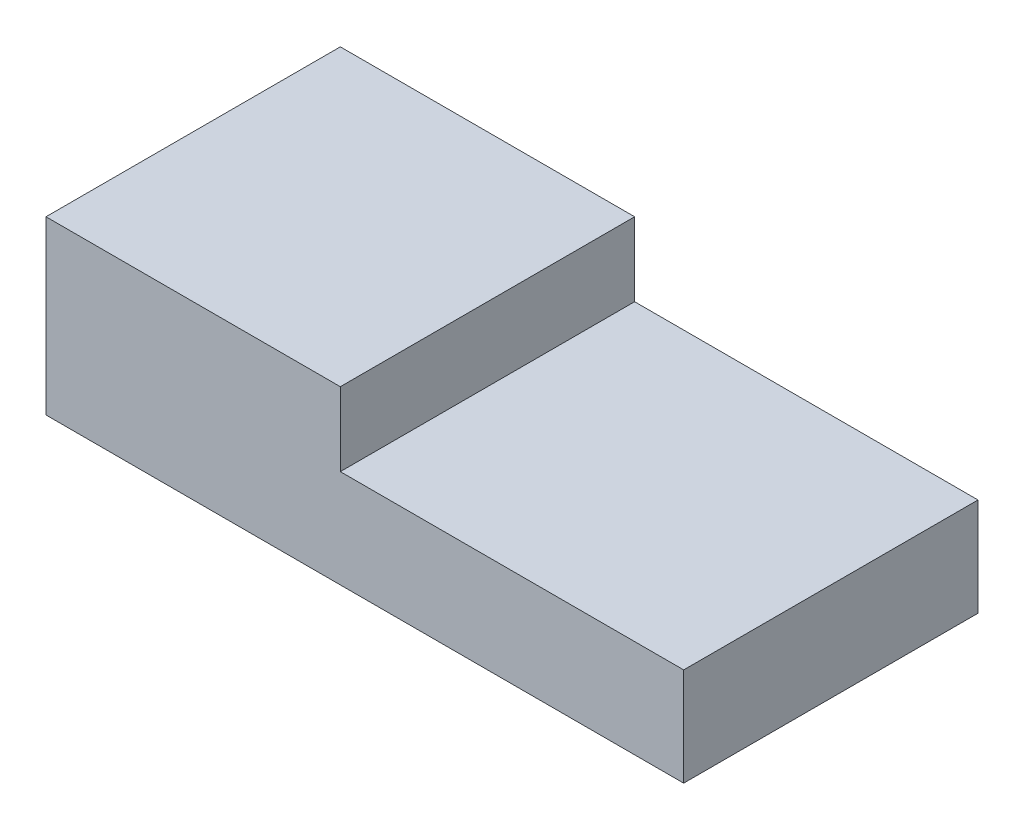
SolidWorks part; units mm, degrees
ref_plane "Front Plane" through (0, 0, 0) normal (0, 0, 1) x (1, 0, 0)
ref_plane "Top Plane" through (0, 0, 0) normal (0, 1, 0) x (1, 0, 0)
ref_plane "Right Plane" through (0, 0, 0) normal (1, 0, 0) x (0, 0, -1)
sketch "Sketch1" plane through (0, 0, 0) normal (1, 0, 0) x (0, 0, -1)
  line L1 (-28.134, 1.866) -> (31.866, 1.866)
  line L2 (-28.134, 1.866) -> (-28.134, -18.134)
  line L3 (-28.134, -18.134) -> (31.866, -18.134)
  line L4 (31.866, 1.866) -> (31.866, -18.134)
  dimension "D1" = 60
  dimension "D2" = 20
extrude "Boss-Extrude1" add sketch "Sketch1" along normal blind 130
sketch "Sketch2" plane through (0, 1.866, 0) normal (0, 1, 0) x (1, 0, 0)
  line L0 (130, -28.134) -> (0, -28.134) construction
  line L1 (0, 31.866) -> (60, 31.866)
  line L2 (0, 31.866) -> (0, -28.134)
  line L3 (0, -28.134) -> (60, -28.134)
  line L4 (60, 31.866) -> (60, -28.134)
  dimension "D1" = 60
extrude "Boss-Extrude2" add sketch "Sketch2" along normal blind 15
